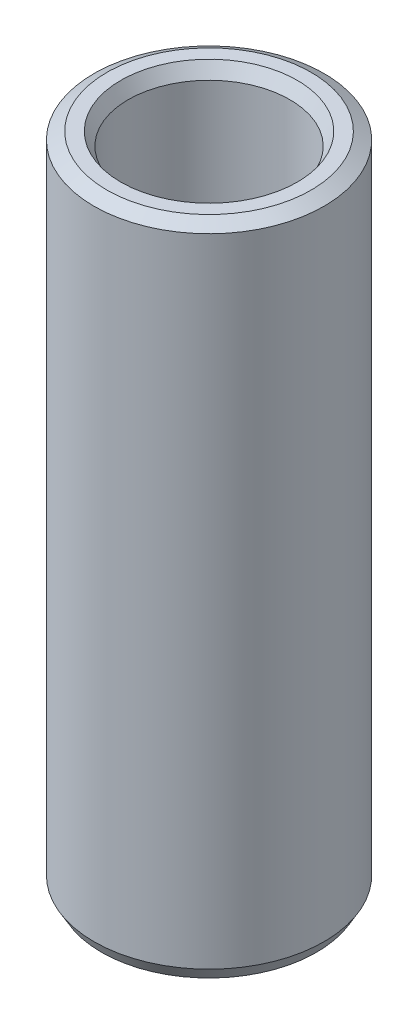
SolidWorks part; units mm, degrees
ref_plane "Front Plane" through (0, 0, 0) normal (0, 0, 1) x (1, 0, 0)
ref_plane "Top Plane" through (0, 0, 0) normal (0, 1, 0) x (1, 0, 0)
ref_plane "Right Plane" through (0, 0, 0) normal (1, 0, 0) x (0, 0, -1)
sketch "Sketch1" plane through (0, 0, 0) normal (0, 1, 0) x (1, 0, 0)
  circle A0 centre (0, 0) radius 35
  dimension "SLEEVE_OD" = 70
extrude "Boss-Extrude1" add sketch "Sketch1" along normal blind 200.018
sketch "Sketch2" plane through (0, 0, 0) normal (0, 1, 0) x (1, 0, 0)
  circle A0 centre (0, 0) radius 24.5726
  dimension "BORE_D" = 49.1452
extrude "Cut-Extrude1" cut sketch "Sketch2" along normal through all
chamfer "Chamfer1" distance 2.2745 angle 60 4 edges at (0, 200.018, 24.5726) (0, 0, 24.5726) (0, 0, 35) (0, 200.018, 35) first distance on face at (0, 200.018, 24.5726) first distance on face at (0, 0, 24.5726) first distance on face at (0, 200.018, 35)
